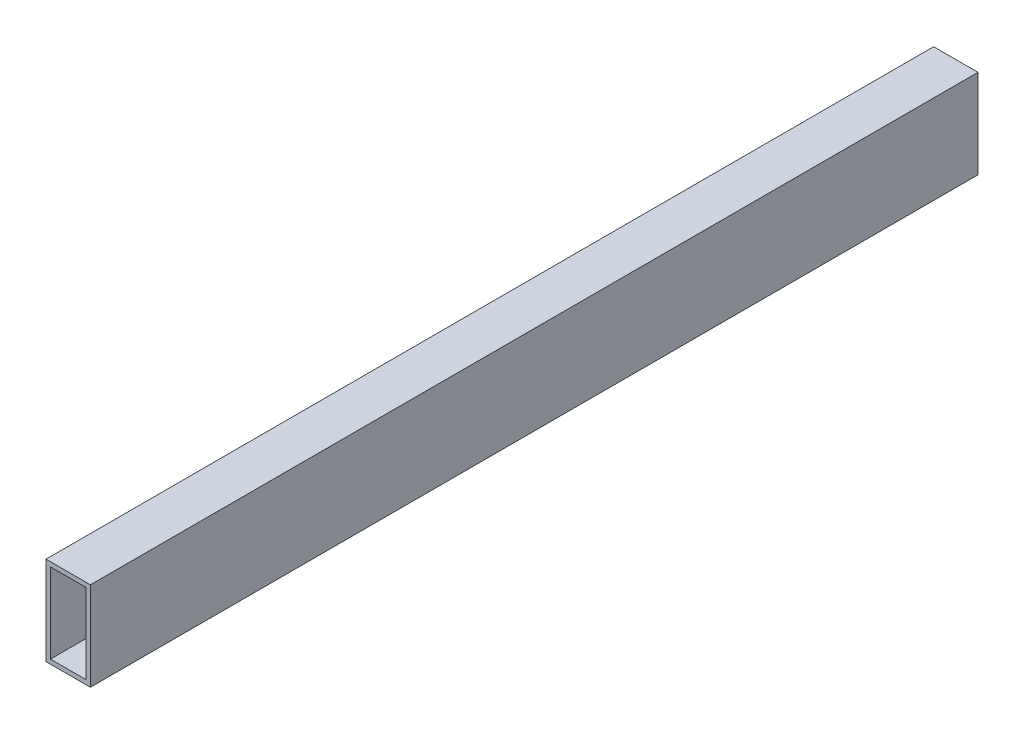
SolidWorks part; units mm, degrees
material "6061-T6 (SS)"
ref_plane "Front" through (0, 0, 0) normal (0, 0, 1) x (1, 0, 0)
ref_plane "Top" through (0, 0, 0) normal (0, 1, 0) x (1, 0, 0)
ref_plane "Right" through (0, 0, 0) normal (1, 0, 0) x (0, 0, -1)
sketch "Sketch1" plane through (0, 0, 0) normal (0, 0, 1) x (1, 0, 0)
  line L1 (-12.7, -25.4) -> (12.7, -25.4)
  line L2 (-12.7, -25.4) -> (-12.7, 25.4)
  line L3 (-12.7, 25.4) -> (12.7, 25.4)
  line L4 (12.7, -25.4) -> (12.7, 25.4)
  line L5 (-12.7, -25.4) -> (12.7, 25.4) construction
  line L6 (-12.7, 25.4) -> (12.7, -25.4) construction
  point P0 (0, 0)
  dimension "D1" = 50.8
  dimension "D2" = 25.4
extrude "Extrude-Thin1" add sketch "Sketch1" along normal blind 508 thin thin type one direction reverse wall 2.54
